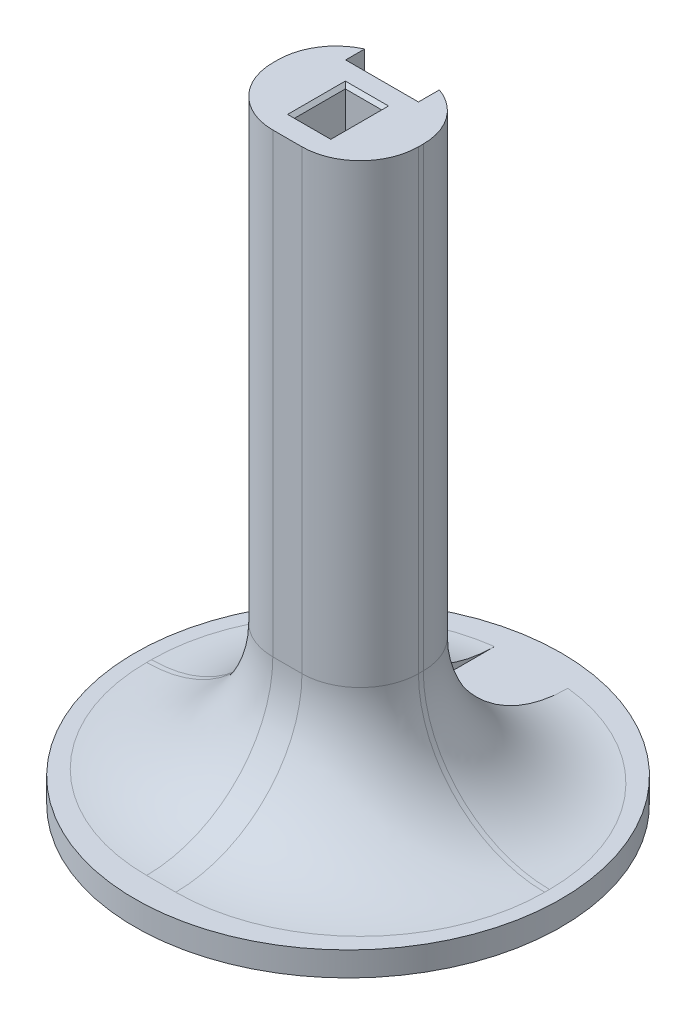
SolidWorks part; units mm, degrees
material "AISI 304"
ref_plane "Front Plane" through (0, 0, 0) normal (0, 0, 1) x (1, 0, 0)
ref_plane "Top Plane" through (0, 0, 0) normal (0, 1, 0) x (1, 0, 0)
ref_plane "Right Plane" through (0, 0, 0) normal (1, 0, 0) x (0, 0, -1)
sketch "Sketch1" plane through (0, 0, 0) normal (0, 1, 0) x (1, 0, 0)
  line L1 (-15, 12.5) -> (15, 12.5)
  line L2 (-15, 12.5) -> (-15, -12.5)
  line L3 (-15, -12.5) -> (15, -12.5)
  line L4 (15, 12.5) -> (15, -12.5)
  line L5 (-15, 12.5) -> (15, -12.5) construction
  line L6 (-15, -12.5) -> (15, 12.5) construction
  point P0 (0, 0)
  dimension "D1" = 25
  dimension "D2" = 30
extrude "Boss-Extrude1" add sketch "Sketch1" along normal blind 120
sketch "Sketch2" plane through (0, 0, 0) normal (0, -1, 0) x (1, 0, 0)
  circle A0 centre (0, 0) radius 43.9139
extrude "Boss-Extrude2" add sketch "Sketch2" along normal blind 5
fillet "Fillet2" radius 12 4 edges at (-15, 60, -12.5) (-15, 60, 12.5) (15, 60, -12.5) (15, 60, 12.5)
sketch "Sketch3" plane through (0, 0, -12.5) normal (0, 0, -1) x (-1, 0, 0)
  line L0 (-3, 120) -> (3, 120) construction
  line L1 (-7, 120) -> (8, 120)
  line L2 (-7, 120) -> (-7, 0.1703)
  line L3 (-7, 0.1703) -> (8, 0.1703)
  line L4 (8, 120) -> (8, 0.1703)
  line L6 (3, 0) -> (3, 120) construction
  dimension "D1" = 15
  dimension "D2" = 5
extrude "Cut-Extrude1" cut sketch "Sketch3" against normal blind 5
sketch "Sketch4" plane through (0, 120, 0) normal (0, 1, 0) x (1, 0, 0)
  line L0 (7, 7.5) -> (-8, 7.5) construction
  line L1 (-3.5608, 3) -> (3.9392, 3)
  line L2 (-3.5608, 3) -> (-3.5608, -7.5)
  line L3 (-3.5608, -7.5) -> (3.9392, -7.5)
  line L4 (3.9392, 3) -> (3.9392, -7.5)
  line L5 (-3.5608, 3) -> (3.9392, -7.5) construction
  line L6 (-3.5608, -7.5) -> (3.9392, 3) construction
  point P0 (0.1892, -2.25)
  dimension "D1" = 10.5
  dimension "D2" = 7.5
  dimension "D3" = 4.5
extrude "Cut-Extrude2" cut sketch "Sketch4" against normal blind 10
chamfer "Chamfer1" distance 0.7 angle 45 4 edges at (0.1892, 120, -3) (3.9392, 120, 2.25) (0.1892, 120, 7.5) (-3.5608, 120, 2.25)
fillet "Fillet3" radius 26 5 edges at (-15, 0, 0) (0, 0, 12.5) (15, 0, 0) (-11.4853, 0, 8.9853) (11.4853, 0, 8.9853)
sketch "Sketch5" plane through (0, -5, 0) normal (0, -1, 0) x (1, 0, 0)
  text T0 "Stand By Earthy"
extrude "Cut-Extrude3" cut sketch "Sketch5" against normal blind 1.5
